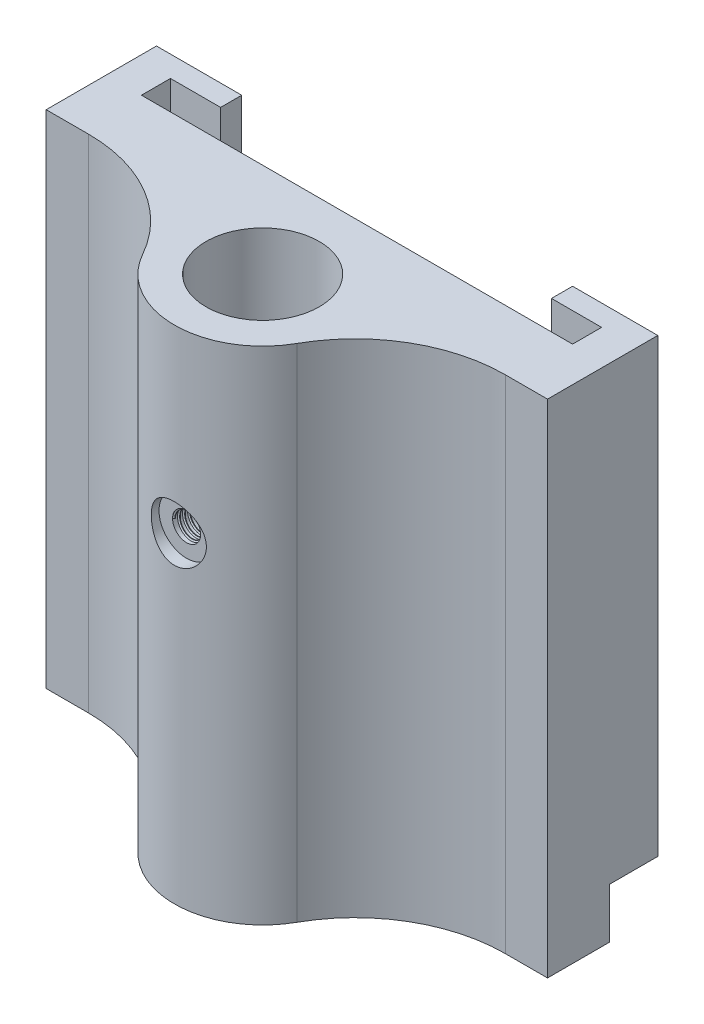
SolidWorks part; units mm, degrees
ref_plane "Front Plane" through (0, 0, 0) normal (0, 0, 1) x (1, 0, 0)
ref_plane "Top Plane" through (0, 0, 0) normal (0, 1, 0) x (1, 0, 0)
ref_plane "Right Plane" through (0, 0, 0) normal (1, 0, 0) x (0, 0, -1)
sketch "Sketch1" plane through (0, 0, 0) normal (0, 1, 0) x (1, 0, 0)
  line L0 (8.5, 0) -> (0, 0)
  line L1 (0, 0) -> (0, -11)
  line L2 (0, -11) -> (50, -11)
  line L3 (50, -11) -> (50, 0)
  line L4 (50, 0) -> (41.5, 0)
  line L6 (46.5, -5) -> (3.5, -5)
  line L8 (3.5, -5) -> (3.5, -2.1045)
  line L9 (3.5, -2.1045) -> (8.5, -2.1045)
  line L10 (8.5, -2.1045) -> (8.5, 0)
  line L11 (46.5, -5) -> (46.5, -2.1045)
  line L12 (46.5, -2.1045) -> (41.5, -2.1045)
  line L13 (41.5, -2.1045) -> (41.5, 0)
  dimension "D2" = 43
  dimension "D3" = 5
  dimension "D4" = 50
  dimension "D5" = 11
extrude "Boss-Extrude1" add sketch "Sketch1" along normal blind 50
sketch "Sketch2" plane through (0, 0, 0) normal (0, -1, 0) x (1, 0, 0)
  line L0 (50, 0) -> (0, 0)
  line L1 (50, 0) -> (41.5, 0) construction
  line L2 (50, 4.8) -> (0, 4.8)
  line L3 (50, 11) -> (50, 0) construction
  line L4 (50, 4.8) -> (50, 0)
  line L5 (0, 0) -> (0, 11) construction
  line L6 (0, 4.8) -> (0, 0)
  dimension "D1" = 4.8
extrude "Cut-Extrude1" cut sketch "Sketch2" against normal blind 5
sketch "Sketch3" plane through (0, 50, 0) normal (0, 1, 0) x (1, 0, 0)
  line L0 (46.5, -5) -> (3.5, -5) construction
  circle A0 centre (25, -14.4123) radius 5.3
  point P7 (25, -5)
  dimension "D2" = 10.6
extrude "Cut-Extrude2" cut sketch "Sketch3" against normal through all
sketch "Sketch5" plane through (0, 50, 0) normal (0, 1, 0) x (1, 0, 0)
  line L0 (16.8885, -11) -> (20.9446, -11)
  line L1 (0, -11) -> (20.9446, -11) construction
  line L2 (29.0554, -11) -> (33.1115, -11)
  line L3 (29.0554, -11) -> (50, -11) construction
  arc A0 (20.9446, -11) -> (29.0554, -11) centre (25, -14.4123) ccw
  arc A1 (16.8885, -11) -> (33.1115, -11) centre (25, -14.4123) ccw
  dimension "D1" = 3.5
extrude "Boss-Extrude2" add sketch "Sketch5" against normal up to surface (50 mm away) up to face at (25, 0, 7.1312)
fillet "Fillet1" radius 15 2 edges at (16.8885, 25, 11) (33.1115, 25, 11)
ref_plane "Plane1" through (0, 0, 27) normal (0, 0, 1) x (1, 0, 0)
sketch "Sketch6" plane through (0, 0, 27) normal (0, 0, 1) x (1, 0, 0)
  line L0 (25, 50) -> (25, 32)
  line L1 (32.6865, 50) -> (17.3135, 50) construction
  circle A0 centre (25, 32) radius 1.4
  dimension "D2" = 2.8
  dimension "D1" = 18
extrude "Cut-Extrude4" cut sketch "Sketch6" against normal blind 10 contours A0
sketch "Sketch7" plane through (0, 0, 27) normal (0, 0, 1) x (1, 0, 0)
  circle A0 centre (25, 32) radius 2.75
  dimension "D1" = 5.5
extrude "Cut-Extrude5" cut sketch "Sketch7" against normal blind 5
thread "Thread1" pitch 0.25 method extrude profile "Thread Profile1" start angle 0, offset 0, length 2.2, pitch 0.5, diameter 2.8
ref_plane "Plane2" through (23.6, 32, 22) normal (0, -1, 0) x (-1, 0, 0)
sketch "Thread Profile1" plane through (23.6, 32, 22) normal (0, -1, 0) x (-1, 0, 0)
  line L0 (0, 0) -> (0, 0.25) construction
  line L11 (0, 0) -> (0, 0.2187)
  line L12 (0, 0.2187) -> (-0.1353, 0.1406)
  line L13 (-0.1353, 0.1406) -> (-0.1353, 0.0781)
  line L15 (-0.1353, 0.0781) -> (0, 0)
  line L17 (-0.1353, 0.1094) -> (0, 0.1094) construction
  point P2 (0, 0)
  dimension "Pitch" = 0.25
  dimension "Profile_Angle" = 60
  dimension "Profile_Land" = 0.0625
  dimension "Profile_Height" = 0.1353
sketch "Sketch9" plane through (0, 50, 0) normal (0, 1, 0) x (1, 0, 0)
  circle A0 centre (25, -14.4123) radius 5.65
  dimension "D1" = 11.3
extrude "Cut-Extrude6" cut sketch "Sketch9" against normal blind 10
equation "\"10mmmm\"=5"
